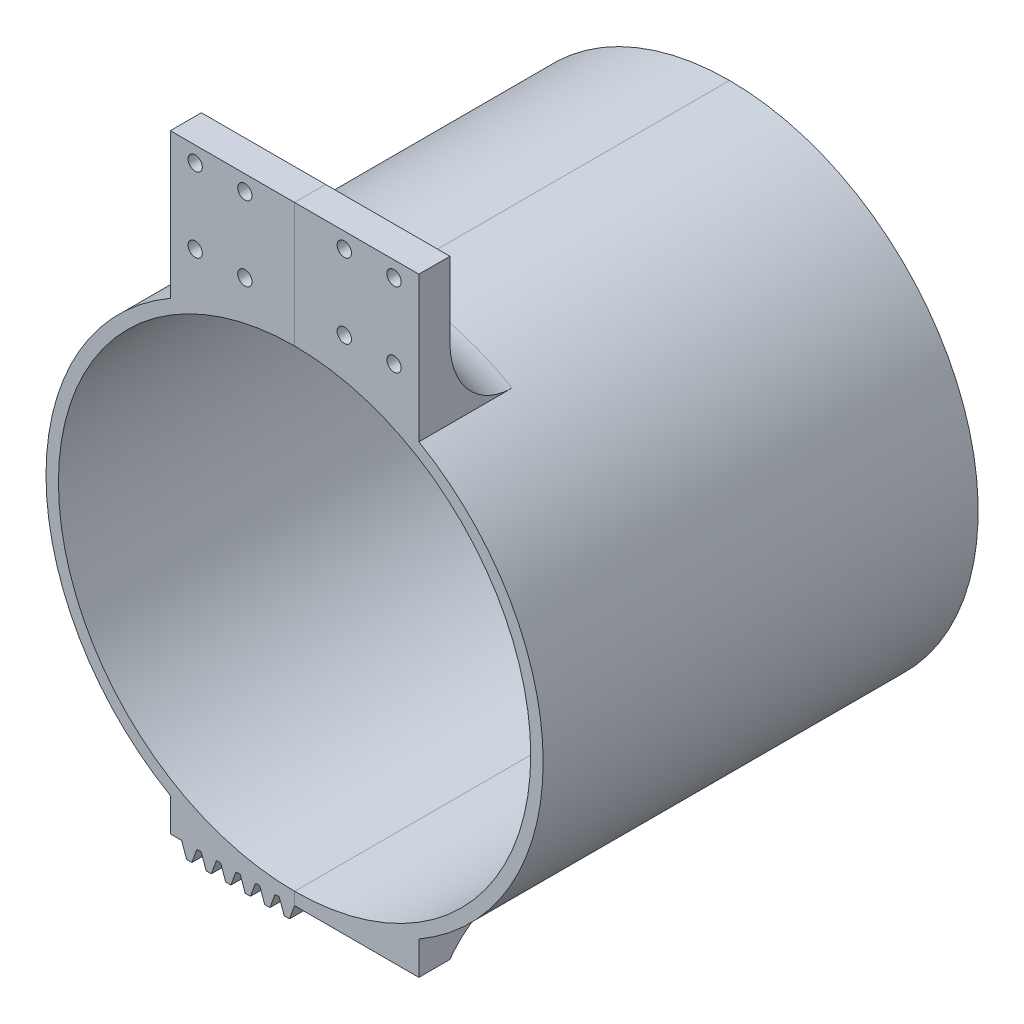
SolidWorks part; units mm, degrees
material "ABS"
ref_plane "前基準面" through (0, 0, 0) normal (0, 0, 1) x (1, 0, 0)
ref_plane "上基準面" through (0, 0, 0) normal (0, 1, 0) x (1, 0, 0)
ref_plane "右基準面" through (0, 0, 0) normal (1, 0, 0) x (0, 0, -1)
sketch "草圖1" plane through (0, 0, 0) normal (0, 0, 1) x (1, 0, 0)
  line L0 (0, 40) -> (0, -40)
  arc A0 (0, 40) -> (0, -40) centre (0, 0) ccw
  dimension "D1" = 40
extrude "填料-伸長1" add sketch "草圖1" along normal blind 70
shell "薄殼1" thickness 2 removed face at (-20, 0, 70) removed face at (0, 0, 35)
sketch "草圖2" plane through (0, 0, 0) normal (0, 0, -1) x (-1, 0, 0)
  line L0 (0, -40) -> (0, 40) construction
  line L3 (5, -37.6696) -> (12, -30.7409)
  line L4 (12, 30.7409) -> (5, 37.6696)
  line L5 (5, 37.6696) -> (5, -37.6696) construction
  line L7 (12, -30.7409) -> (12, 30.7409) construction
  line L8 (0, -38) -> (0, 38)
  arc A0 (12, 30.7409) -> (12, -30.7409) centre (0, 0) cw
  arc A1 (0, -38) -> (5, -37.6696) centre (0, 0) ccw
  arc A2 (5, 37.6696) -> (0, 38) centre (0, 0) ccw
  dimension "D2" = 33
  dimension "D4" = 5
  dimension "D3" = 38
  dimension "D1" = 7
extrude "除料-伸長1" cut sketch "草圖2" against normal blind 75
sketch "草圖5" plane through (0, 0, 70) normal (0, 0, 1) x (1, 0, 0)
  line L0 (0, -40) -> (-20, -40)
  line L4 (-20, -40) -> (-20, -34.641)
  arc A0 (0, 40) -> (0, -40) centre (0, 0) ccw construction
  arc A1 (0, -40) -> (-20, -34.641) centre (0, 0) cw
  arc M8 (0, 40) -> (0, -40) centre (0, 0) ccw
  dimension "D1" = 20
extrude "填料-伸長2" add sketch "草圖5" against normal blind 5 contours L4 L0 M8 region at (-15.0695, -38.4126, 70)
sketch "草圖6" plane through (0, 0, 70) normal (0, 0, 1) x (1, 0, 0)
  line L0 (0, 40) -> (0, 58)
  line L1 (0, 58) -> (-20, 58)
  line L2 (-20, 58) -> (-20, 40)
  line L3 (-20, 40) -> (0, 40)
  line L4 (-20, 40) -> (-20, 34.641)
  arc A0 (0, 40) -> (-20, -34.641) centre (0, 0) ccw construction
  arc A1 (0, 40) -> (-20, 34.641) centre (0, 0) ccw
  arc M7 (0, 40) -> (-20, -34.641) centre (0, 0) ccw
  dimension "D1" = 18
  dimension "D2" = 20
extrude "填料-伸長3" add sketch "草圖6" against normal blind 5 contours L3 L4 M7 | L2 L3 L0 L1 region at (-10, 49, 70) region at (-15.0695, 38.4126, 70)
fillet "圓角1" radius 10 2 edges at (-10.3528, -38.637, 65) (-10.3528, 38.637, 65)
hole_wizard "M2.2 螺旋的螺孔鑽1" positions "草圖11" profile "草圖12" hole size "M2.2x0.45" standard "Ansi Metric" end condition through all
sketch "草圖11" plane through (0, 0, 0) normal (0, 0, -1) x (-1, 0, 0)
  line L1 (8, 55.5) -> (16, 55.5) construction
  line L2 (8, 55.5) -> (8, 43.5) construction
  line L3 (8, 43.5) -> (16, 43.5) construction
  line L4 (16, 55.5) -> (16, 43.5) construction
  line L5 (8, 55.5) -> (16, 43.5) construction
  line L6 (8, 43.5) -> (16, 55.5) construction
  line L7 (0, 58) -> (20, 58) construction
  line L8 (20, 58) -> (20, 34.641) construction
  point P2 (16, 43.5)
  point P81 (8, 55.5)
  point P82 (8, 43.5)
  point P83 (16, 55.5)
  dimension "D1" = 8
  dimension "D2" = 12
  dimension "D3" = 2.5
  dimension "D4" = 4
sketch "草圖12" plane through (-16, 43.5, 0) normal (1, 0, 0) x (0, 1, 0)
  line L0 (0, 0) -> (0, 70)
  line L1 (0, 70) -> (1.15, 70)
  line L2 (1.15, 70) -> (1.15, 0)
  line L5 (1.15, 0) -> (0, 0)
  line L11 (0, -6.35) -> (0, 107.95) construction
  dimension "貫穿孔直徑" = 2.3
  dimension "貫穿孔深度" = 70
sketch "草圖15" plane through (0, 0, 65) normal (0, 0, -1) x (-1, 0, 0)
  circle A0 centre (16, 43.5) radius 2.6
  circle A1 centre (8, 43.5) radius 2.6
  dimension "D1" = 5.2
extrude "除料-伸長2" cut sketch "草圖15" along normal through all
sketch "草圖16" plane through (0, 0, 0) normal (0, 0, -1) x (-1, 0, 0)
  arc A0 (12, -30.7409) -> (12, 30.7409) centre (-8, 0) ccw
  arc A1 (12, -30.7409) -> (12, 30.7409) centre (0, 0) ccw
  arc A2 (12, -30.7409) -> (12, 30.7409) centre (0, 0) ccw construction
  point P4 (0, 0)
  point P8 (0, 0)
  point P13 (0, 0)
  arc M8 (12, 30.7409) -> (12, -30.7409) centre (0, 0) cw
  dimension "D1" = 8
extrude "填料-伸長7" add sketch "草圖16" against normal up to surface (2 mm away) contours A0 M8 region at (-29.3239, 0, 0) up to face at (-22, 0, 2)
mirror "鏡射1" about plane through (0, 40, 70) normal (-1, 0, 0) of bodies 116 103
sketch "草圖13" plane through (0, 0, 70) normal (0, 0, 1) x (1, 0, 0)
  line L0 (0, -40) -> (-2.4807, -40)
  line L2 (-2.4807, -40) -> (-1.6618, -42.25)
  line L3 (-1.6618, -42.25) -> (-0.8189, -42.25)
  line L4 (-0.8189, -42.25) -> (0, -40)
  line L5 (-1.2404, -40) -> (-1.2404, -42.25) construction
  line L6 (-2.0258, -41.25) -> (-0.455, -41.25) construction
  line L8 (0, -40) -> (-20, -40) construction
  dimension "D1" = 40
  dimension "D2" = 2.25
  dimension "D3" = 1.5708
  dimension "D4" = 1
extrude "填料-伸長6" add sketch "草圖13" against normal blind 5
pattern_linear "直線複製排列1" count 6 spacing 3.1416 along (-1, 0, 0) of "填料-伸長6"
equation "\"M\"=1"
equation "\"D2@草圖13\"=\"M\"*2.25"
equation "\"D3@草圖13\"=\"M\"*PI/2"
equation "\"D4@草圖13\"=\"M\"*1"
equation "\"D3@直線複製排列1\"=\"M\"*PI"
